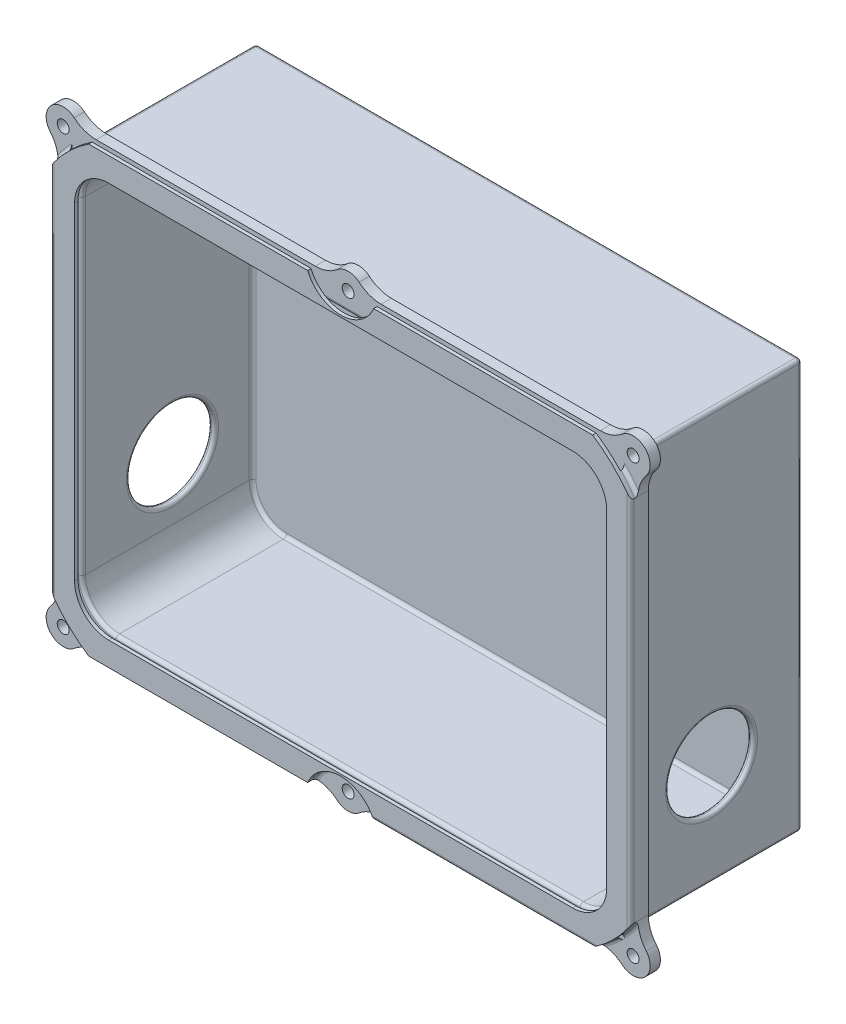
SolidWorks part; units mm, degrees
ref_plane "Front Plane" through (0, 0, 0) normal (0, 0, 1) x (1, 0, 0)
ref_plane "Top Plane" through (0, 0, 0) normal (0, 1, 0) x (1, 0, 0)
ref_plane "Right Plane" through (0, 0, 0) normal (1, 0, 0) x (0, 0, -1)
sketch "Sketch1" plane through (0, 0, 0) normal (0, 0, 1) x (1, 0, 0)
  line L1 (-44, 54) -> (44, 54)
  line L2 (-44, 54) -> (-44, -54)
  line L3 (-44, -54) -> (44, -54)
  line L4 (44, 54) -> (44, -54)
  line L5 (-44, 54) -> (44, -54) construction
  line L6 (-44, -54) -> (44, 54) construction
  point P0 (0, 0)
  dimension "D1" = 108
  dimension "D2" = 88
sketch "Sketch2" plane through (0, 0, 0) normal (0, 0, 1) x (1, 0, 0)
  line L1 (-80, 60) -> (80, 60)
  line L2 (-80, 60) -> (-80, -60)
  line L3 (-80, -60) -> (80, -60)
  line L4 (80, 60) -> (80, -60)
  line L5 (-80, 60) -> (80, -60) construction
  line L6 (-80, -60) -> (80, 60) construction
  point P0 (0, 0)
  dimension "D1" = 120
  dimension "D2" = 160
extrude "Boss-Extrude1" add sketch "Sketch2" along normal blind 3
sketch "Sketch3" plane through (0, 0, 3) normal (0, 0, 1) x (1, 0, 0)
  line L1 (-80, 60) -> (80, 60)
  line L2 (-80, 60) -> (-80, -60)
  line L3 (-80, -60) -> (80, -60)
  line L4 (80, 60) -> (80, -60)
  line L5 (-80, 60) -> (80, -60) construction
  line L6 (-80, -60) -> (80, 60) construction
  line L8 (-78, 58) -> (78, 58)
  line L9 (-78, 58) -> (-78, -58)
  line L10 (-78, -58) -> (78, -58)
  line L11 (78, 58) -> (78, -58)
  line L12 (-78, 58) -> (78, -58) construction
  line L13 (-78, -58) -> (78, 58) construction
  point P0 (0, 0)
  point P11 (-90, 60)
  dimension "D1" = 2
  dimension "D2" = 2
extrude "Boss-Extrude2" add sketch "Sketch3" along normal blind 50
sketch "Sketch5" plane through (0, 0, 0) normal (1, 0, 0) x (0, 0, -1)
  line L0 (-53, -60) -> (0, 60) construction
  line L1 (-26.5, -30) -> (-26.5, 0) construction
  line L2 (0, 0) -> (-53, 0) construction
  line L3 (0, -60) -> (0, 60) construction
  line L4 (-53, -60) -> (-53, 60) construction
  line L5 (-53, 0) -> (0, -60) construction
  circle A0 centre (-26.5, -30) radius 12.5
  point P6 (-26.5, -30)
  dimension "D1" = 25
extrude "Cut-Extrude1" cut sketch "Sketch5" against normal through all both and the other way through all
sketch "Sketch6" plane through (0, 0, 53) normal (0, 0, 1) x (1, 0, 0)
  line L0 (80, -60) -> (80, 60) construction
  line L1 (-85, -65) -> (85, -65)
  line L2 (-85, -65) -> (-85, 65)
  line L3 (-85, 65) -> (85, 65)
  line L4 (85, -65) -> (85, 65)
  line L5 (-85, -65) -> (85, 65) construction
  line L6 (-85, 65) -> (85, -65) construction
  line L7 (-78, -58) -> (78, -58)
  line L8 (-78, -58) -> (-78, 58)
  line L9 (-78, 58) -> (78, 58)
  line L10 (78, -58) -> (78, 58)
  line L11 (-78, -58) -> (78, 58) construction
  line L12 (-78, 58) -> (78, -58) construction
  line L13 (80, 60) -> (-80, 60) construction
  point P0 (0, 0)
  point P6 (0, 0)
  dimension "D1" = 5
  dimension "D2" = 5
extrude "Boss-Extrude3" add sketch "Sketch6" against normal blind 3
sketch "Sketch8" plane through (0, 0, 53) normal (0, 0, 1) x (1, 0, 0)
  line L0 (85.985, 65.985) -> (85, 65) construction
  line L1 (81.086, 61.086) -> (84.4321, 60.1895)
  line L2 (84.4321, 60.1895) -> (86.8816, 62.639)
  line L3 (86.8816, 62.639) -> (85.985, 65.985)
  line L4 (85.985, 65.985) -> (82.639, 66.8816)
  line L5 (82.639, 66.8816) -> (80.1895, 64.4321)
  line L6 (80.1895, 64.4321) -> (81.086, 61.086)
  line L7 (85, 65) -> (80, 60) construction
  line L8 (0, 0) -> (85, 0) construction
  line L9 (85, -65) -> (85, 65) construction
  line L10 (0, 0) -> (0, 65) construction
  line L11 (85, 65) -> (-85, 65) construction
  line L12 (83.5355, 68.5355) -> (0, 68.5355) construction
  line L13 (-85, 65) -> (-80, 60) construction
  line L14 (-3.4641, 63.5355) -> (-1.7321, 60.5355)
  line L15 (-1.7321, 60.5355) -> (1.7321, 60.5355)
  line L16 (1.7321, 60.5355) -> (3.4641, 63.5355)
  line L17 (3.4641, 63.5355) -> (1.7321, 66.5355)
  line L18 (1.7321, 66.5355) -> (-1.7321, 66.5355)
  line L19 (-1.7321, 66.5355) -> (-3.4641, 63.5355)
  line L20 (-85.985, 65.985) -> (-85, 65) construction
  line L21 (-80.1895, 64.4321) -> (-81.086, 61.086)
  line L22 (-82.639, 66.8816) -> (-80.1895, 64.4321)
  line L23 (-85.985, 65.985) -> (-82.639, 66.8816)
  line L24 (-86.8816, 62.639) -> (-85.985, 65.985)
  line L25 (-84.4321, 60.1895) -> (-86.8816, 62.639)
  line L26 (-81.086, 61.086) -> (-84.4321, 60.1895)
  line L27 (-85.985, -65.985) -> (-85, -65) construction
  line L28 (-85, -65) -> (-80, -60) construction
  line L29 (-81.086, -61.086) -> (-84.4321, -60.1895)
  line L30 (-84.4321, -60.1895) -> (-86.8816, -62.639)
  line L31 (-86.8816, -62.639) -> (-85.985, -65.985)
  line L32 (-85.985, -65.985) -> (-82.639, -66.8816)
  line L33 (-82.639, -66.8816) -> (-80.1895, -64.4321)
  line L34 (-80.1895, -64.4321) -> (-81.086, -61.086)
  line L35 (85, -65) -> (80, -60) construction
  line L36 (85.985, -65.985) -> (85, -65) construction
  line L37 (80.1895, -64.4321) -> (81.086, -61.086)
  line L38 (82.639, -66.8816) -> (80.1895, -64.4321)
  line L39 (85.985, -65.985) -> (82.639, -66.8816)
  line L40 (86.8816, -62.639) -> (85.985, -65.985)
  line L41 (84.4321, -60.1895) -> (86.8816, -62.639)
  line L42 (81.086, -61.086) -> (84.4321, -60.1895)
  line L43 (-1.7321, -66.5355) -> (-3.4641, -63.5355)
  line L44 (1.7321, -66.5355) -> (-1.7321, -66.5355)
  line L45 (3.4641, -63.5355) -> (1.7321, -66.5355)
  line L46 (1.7321, -60.5355) -> (3.4641, -63.5355)
  line L47 (-1.7321, -60.5355) -> (1.7321, -60.5355)
  line L48 (-3.4641, -63.5355) -> (-1.7321, -60.5355)
  circle A0 centre (83.5355, 63.5355) radius 3 construction
  circle A1 centre (83.5355, 63.5355) radius 5
  circle A2 centre (0, 63.5355) radius 5
  circle A3 centre (0, 63.5355) radius 3 construction
  circle A4 centre (-83.5355, 63.5355) radius 3 construction
  circle A5 centre (-83.5355, 63.5355) radius 5
  circle A6 centre (-83.5355, -63.5355) radius 3 construction
  circle A7 centre (-83.5355, -63.5355) radius 5
  circle A8 centre (83.5355, -63.5355) radius 3 construction
  circle A9 centre (83.5355, -63.5355) radius 5
  circle A10 centre (0, -63.5355) radius 3 construction
  circle A11 centre (0, -63.5355) radius 5
  point P26 (0, 0)
  line M24 (85, -65) -> (85, 65)
  line M25 (85, 65) -> (-85, 65)
  line M26 (-85, 65) -> (-85, -65)
  line M27 (-85, -65) -> (85, -65)
  dimension "D1" = 6
  dimension "D2" = 10
  dimension "D3" = 10
  dimension "D4" = 6
extrude "Boss-Extrude4" add sketch "Sketch8" against normal blind 3 contours L4 L5 L2 L3 M25 M24 | A1 L5 L4 L3 L2 M24 M25 | A9 L41 L40 L39 L38 M24 M27 | L41 L38 L39 L40 M24 M27 | L32 L33 L30 L31 M27 M26 | A7 L33 L32 L31 L30 M26 M27 | L45 L43 L44 M27 | A11 L45 L44 L43 M27 | A2 L19 L18 L17 M25 | L18 L19 L17 M25 | A5 L25 L24 L23 L22 M26 M25 | L25 L22 L23 L24 M26 M25 region at (85.0866, 62.8787, 53) region at (86.0386, 61.6004, 53) region at (87.4444, -60.6448, 53) region at (0, 66.7453, 53) region at (85.8796, -61.7594, 53) region at (0, 65.7156, 53) region at (0, -66.7453, 53) region at (-79.7561, 65.1383, 53) region at (0, -65.7156, 53) region at (-82.8787, 65.0866, 53) region at (-86.9733, -66.9733, 53) region at (-81.7594, -65.8796, 53)
sketch "Sketch9" plane through (0, 0, 50) normal (0, 0, -1) x (-1, 0, 0)
  circle A0 centre (-83.5355, 63.5355) radius 1.75
  circle A1 centre (-83.5355, -63.5355) radius 1.75
  circle A2 centre (0, -63.5355) radius 1.75
  circle A3 centre (83.5355, -63.5355) radius 1.75
  circle A4 centre (83.5355, 63.5355) radius 1.75
  circle A5 centre (0, 63.5355) radius 1.75
  arc A6 (4.7807, 65) -> (-4.7807, 65) centre (0, 63.5355) ccw construction
  arc A7 (-78.7548, 65) -> (-85, 58.7548) centre (-83.5355, 63.5355) ccw construction
  arc A8 (-85, -58.7548) -> (-78.7548, -65) centre (-83.5355, -63.5355) ccw construction
  arc A9 (78.7548, -65) -> (85, -58.7548) centre (83.5355, -63.5355) ccw construction
  arc A10 (85, 58.7548) -> (78.7548, 65) centre (83.5355, 63.5355) ccw construction
  arc A11 (-4.7807, -65) -> (4.7807, -65) centre (0, -63.5355) ccw construction
  dimension "D1" = 3.5
extrude "Cut-Extrude2" cut sketch "Sketch9" against normal through all
fillet "Fillet1" radius 10 12 edges at (-4.7807, -65, 51.5) (4.7807, -65, 51.5) (78.7548, -65, 51.5) (85, -58.7548, 51.5) (85, 58.7548, 51.5) (78.7548, 65, 51.5) (4.7807, 65, 51.5) (-4.7807, 65, 51.5) (-78.7548, 65, 51.5) (-85, -58.7548, 51.5) (-78.7548, -65, 51.5) (-85, 58.7548, 51.5)
sketch "Sketch12" plane through (0, 0, 53) normal (0, 0, 1) x (1, 0, 0)
  line L0 (-85, 53.8626) -> (-85, -53.8626) construction
  line L1 (78, -58) -> (-78, -58)
  line L2 (78, -58) -> (78, 58)
  line L3 (78, 58) -> (-78, 58)
  line L4 (-78, -58) -> (-78, 58)
  line L5 (78, -58) -> (-78, 58) construction
  line L6 (78, 58) -> (-78, -58) construction
  line L7 (85, -65) -> (-85, -65)
  line L8 (85, -65) -> (85, 65)
  line L9 (85, 65) -> (-85, 65)
  line L10 (-85, -65) -> (-85, 65)
  line L11 (85, -65) -> (-85, 65) construction
  line L12 (85, 65) -> (-85, -65) construction
  line L13 (-9.673, 65) -> (-73.8626, 65) construction
  line L14 (0, 0) -> (0, 58) construction
  line L15 (0, 0) -> (78, 0) construction
  arc A1 (-73.8626, 65) -> (-85, 53.8626) centre (-52.4517, 32.4517) ccw
  circle A2 centre (-83.5355, 63.5355) radius 5
  arc A3 (-80.3112, 67.357) -> (-87.357, 60.3112) centre (-83.5355, 63.5355) ccw construction
  arc A4 (73.8626, 65) -> (85, 53.8626) centre (52.4517, 32.4517) cw
  arc A5 (-73.8626, -65) -> (-85, -53.8626) centre (-52.4517, -32.4517) cw
  arc A6 (73.8626, -65) -> (85, -53.8626) centre (52.4517, -32.4517) ccw
  circle A7 centre (0, 63.5355) radius 5
  arc A9 (3.2243, 67.357) -> (-3.2243, 67.357) centre (0, 63.5355) ccw construction
  circle A10 centre (0, -63.5355) radius 5
  arc A11 (-3.2243, -67.357) -> (3.2243, -67.357) centre (0, -63.5355) ccw construction
  arc A12 (-9.673, -65) -> (9.673, -65) centre (0, -69.0047) cw
  arc A13 (-9.673, 65) -> (9.673, 65) centre (0, 69.0047) ccw
  point P0 (0, 0)
  point P6 (0, 0)
  circle M13 centre (0, -63.5355) radius 1.75
  circle M16 centre (0, 63.5355) radius 1.75
  line M18 (-85, 53.8626) -> (-85, -53.8626)
  line M22 (-73.8626, -65) -> (-9.673, -65)
  line M26 (9.673, -65) -> (73.8626, -65)
  line M30 (85, -53.8626) -> (85, 53.8626)
  line M34 (73.8626, 65) -> (9.673, 65)
  line M38 (-9.673, 65) -> (-73.8626, 65)
  line M42 (-78, 58) -> (78, 58)
  line M43 (78, 58) -> (78, -58)
  line M44 (78, -58) -> (-78, -58)
  line M45 (-78, -58) -> (-78, 58)
extrude "Boss-Extrude5" add sketch "Sketch12" along normal blind 2.2 contours A6 A4 L9 A1 A5 L7 M26 M30 M34 M16 M38 M18 M22 M13 M45 M42 M43 M44 region at (41.7678, -62.8599, 53)
fillet "Fillet3" radius 10 4 edges at (78, 58, 29.1) (78, -58, 29.1) (-78, -58, 29.1) (-78, 58, 29.1)
sketch "Sketch13" plane through (0, 0, 53) normal (0, 0, 1) x (1, 0, 0)
  line L0 (78, 48) -> (78, -48) construction
  line L1 (-81, -61) -> (81, -61)
  line L2 (-81, -61) -> (-81, 65)
  line L3 (-81, 65) -> (81, 65)
  line L4 (81, -61) -> (81, 65)
  line L5 (-78, 48) -> (-78, -48) construction
  line L6 (68, -58) -> (-68, -58) construction
  line L7 (73.8626, 65) -> (9.673, 65) construction
  point P8 (0, 0)
  point P9 (0, 0)
  point P16 (0, 0)
  point P17 (53.3128, 9.8089)
  dimension "D1" = 3
  dimension "D2" = 3
  dimension "D3" = 3
extrude "Cut-Extrude3" cut sketch "Sketch13" along normal blind 1.2
fillet "Fillet4" radius 1 43 edges at (-75.0711, -55.0711, 53) (0, -58, 53) (75.0711, -55.0711, 53) (78, 0, 53) (75.0711, 55.0711, 53) (0, 58, 53) (-75.0711, 55.0711, 53) (0, 60, 50) (-80, 60, 25) (-80, 0, 50) (-80, -60, 25) (0, -60, 50) (80, -60, 25) (80, 0, 50) (80, 60, 25) (0, 60, 0) (-80, 0, 0) (0, -60, 0) (80, 0, 0) (80, -30, 14) (78, -30, 39) (-80, -30, 14) (-78, -30, 14) (75.0711, -55.0711, 3) (0, -58, 3) (-75.0711, -55.0711, 3) (-78, 0, 3) (-75.0711, 55.0711, 3) (0, 58, 3) (75.0711, 55.0711, 3) (78, 0, 3) (83.1062, 56.4958, 53) (83.1062, -56.4958, 53) (76.4958, -63.1062, 53) (8.4503, -62.8244, 53) (-8.4503, -62.8244, 53) (-76.4958, -63.1062, 53) (-83.1062, -56.4958, 53) (-83.1062, 56.4958, 53) (-78, 0, 53) (41.7678, -65, 55.2) (85, 0, 55.2) (-85, 0, 55.2)
